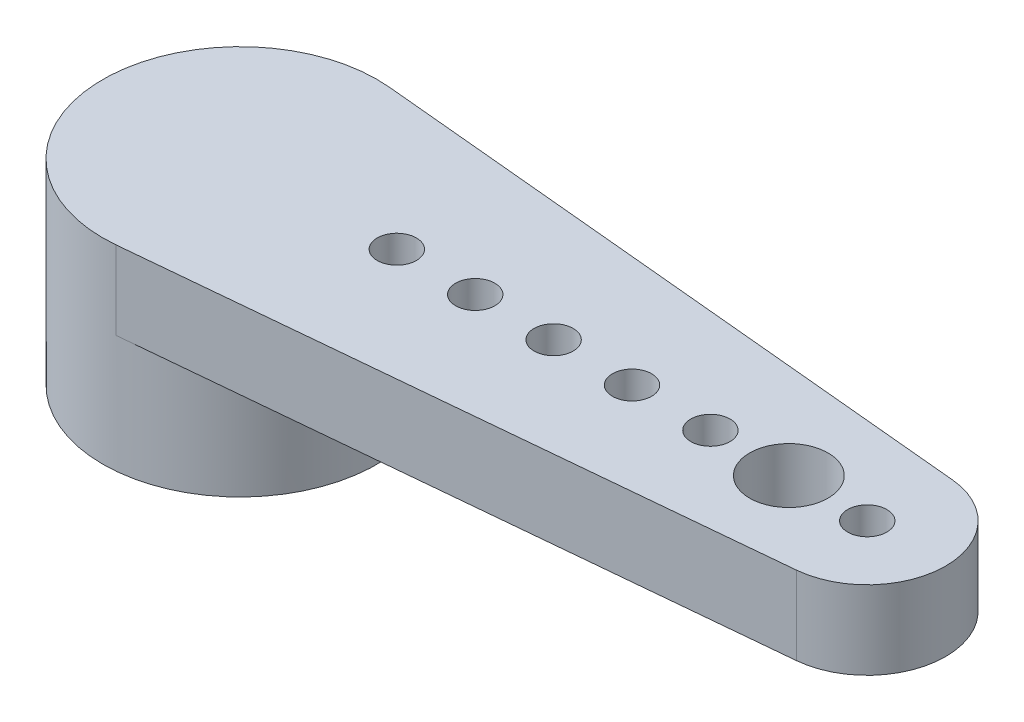
SolidWorks part; units mm, degrees
material "ABS"
ref_plane "Front Plane" through (0, 0, 0) normal (0, 0, 1) x (1, 0, 0)
ref_plane "Top Plane" through (0, 0, 0) normal (0, 1, 0) x (1, 0, 0)
ref_plane "Right Plane" through (0, 0, 0) normal (1, 0, 0) x (0, 0, -1)
sketch "Sketch1" plane through (0, 0, 0) normal (0, 1, 0) x (1, 0, 0)
  circle A0 centre (0, 0) radius 3.5
  circle A1 centre (0, 0) radius 2.4
  dimension "D1" = 7
  dimension "D2" = 4.8
extrude "Boss-Extrude1" add sketch "Sketch1" along normal blind 3
sketch "Sketch2" plane through (0, 3, 0) normal (0, 1, 0) x (1, 0, 0)
  line L0 (0.3281, 3.4846) -> (16.1875, 1.9912)
  line L1 (0.3281, -3.4846) -> (16.1875, -1.9912)
  line L2 (12, 0) -> (10, 0) construction
  circle A0 centre (16, 0) radius 2
  circle A1 centre (0, 0) radius 3.5 construction
  circle A2 centre (0, 0) radius 3.5
  circle A3 centre (16, 0) radius 0.5
  circle A4 centre (14, 0) radius 1
  circle A5 centre (12, 0) radius 0.5
  circle A6 centre (10, 0) radius 0.5
  circle A7 centre (8, 0) radius 0.5
  circle A8 centre (6, 0) radius 0.5
  circle A9 centre (4, 0) radius 0.5
  circle M1 centre (0, 0) radius 3.5
  circle M2 centre (0, 0) radius 2.4
  dimension "D1" = 4
  dimension "D2" = 16
  dimension "D3" = 1
  dimension "D4" = 2
  dimension "D6" = 1
  dimension "D5" = 2
  dimension "D7" = 2
  dimension "D9" = 2
  dimension "D8" = 5
extrude "Boss-Extrude2" add sketch "Sketch2" along normal blind 2 contours A2 M1 M2 | A2 A9 L1 A0 A4 L0 A8 A7 A5 A6 M1 | A4 A0 A3 | M2 region at (8.2416, 3, -2.5654) region at (2.5151, 3, -2.2894) region at (17.4385, 3, -1.3094) region at (0, 3, 0)
ref_axis "Axis1" through (14, 5, 0) along (0, -1, 0)
